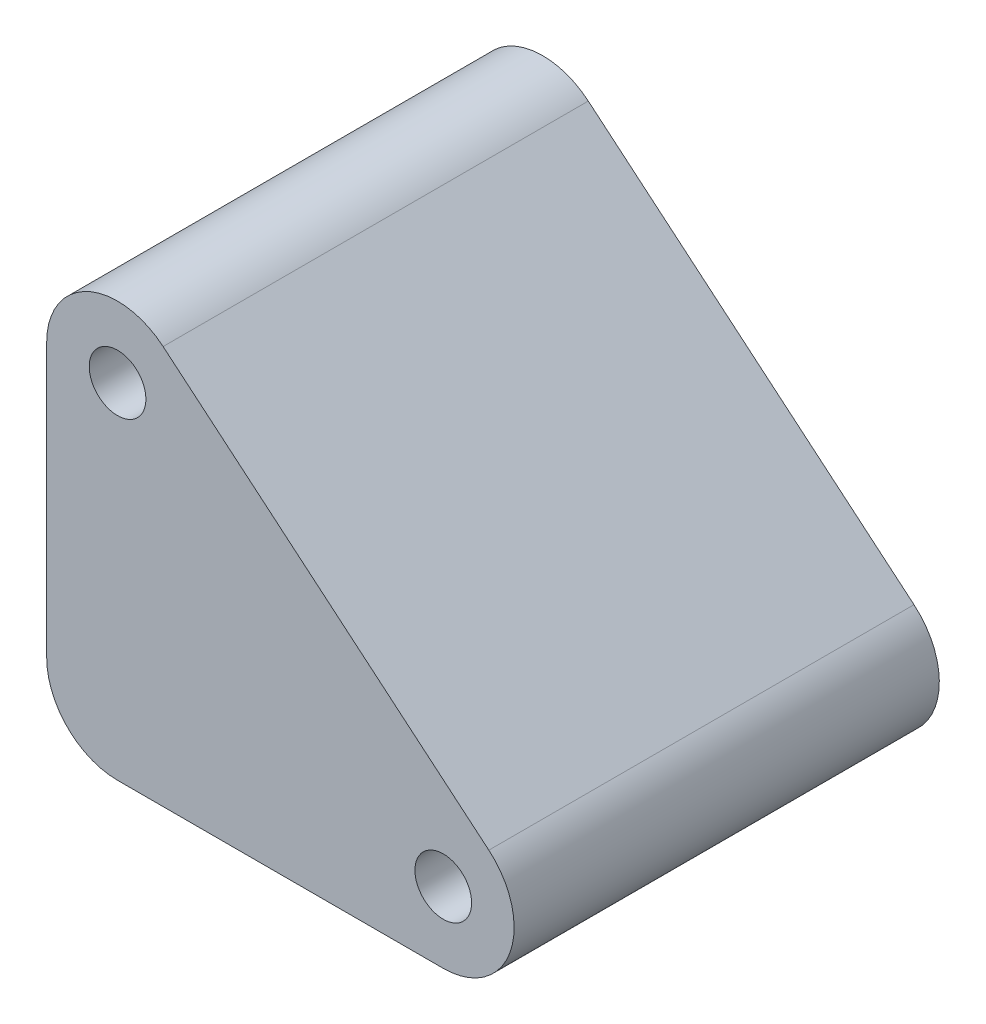
SolidWorks part; units mm, degrees
ref_plane "Front Plane" through (0, 0, 0) normal (0, 0, 1) x (1, 0, 0)
ref_plane "Top Plane" through (0, 0, 0) normal (0, 1, 0) x (1, 0, 0)
ref_plane "Right Plane" through (0, 0, 0) normal (1, 0, 0) x (0, 0, -1)
sketch "Sketch1" plane through (0, 0, 0) normal (0, 0, 1) x (1, 0, 0)
  line L0 (-269.7441, 37.9811) -> (-246.7628, 18.6974)
  line L1 (-249.9767, 9.8672) -> (-272.9581, 9.8672)
  line L2 (-277.9581, 14.8672) -> (-277.9581, 34.1509)
  circle A0 centre (-249.9767, 14.8672) radius 2 construction
  circle A1 centre (-272.9581, 34.1509) radius 2 construction
  circle A2 centre (-249.9767, 14.8672) radius 2
  circle A3 centre (-272.9581, 34.1509) radius 2
  arc A4 (-246.7628, 18.6974) -> (-249.9767, 9.8672) centre (-249.9767, 14.8672) cw
  arc A5 (-272.9581, 9.8672) -> (-277.9581, 14.8672) centre (-272.9581, 14.8672) cw
  arc A6 (-277.9581, 34.1509) -> (-269.7441, 37.9811) centre (-272.9581, 34.1509) cw
  dimension "D1" = 5
  dimension "D2" = 5
  dimension "D3" = 5
  dimension "D4" = 19.2836
  dimension "D5" = 22.9813
extrude "Boss-Extrude1" add sketch "Sketch1" along normal blind 15 and the other way blind 15
